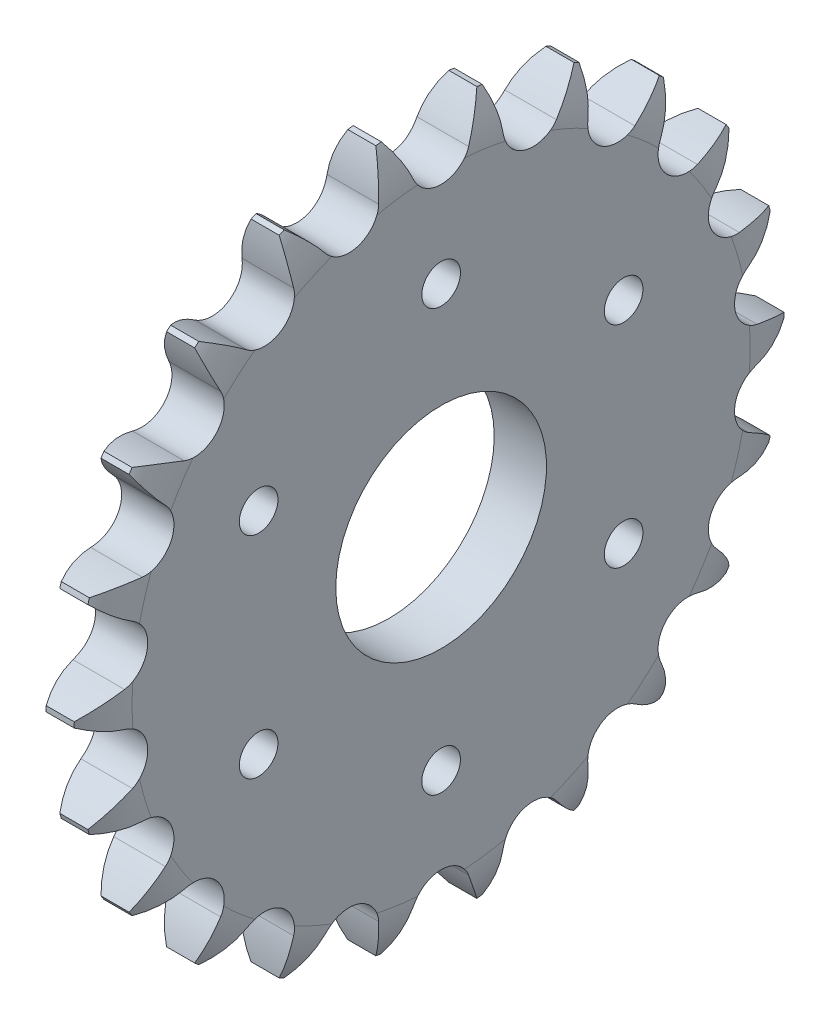
SolidWorks part; units mm, degrees
ref_plane "Plane1" through (0, 0, 0) normal (0, 0, 1) x (1, 0, 0)
ref_plane "Plane2" through (0, 0, 0) normal (0, 1, 0) x (1, 0, 0)
ref_plane "Plane3" through (0, 0, 0) normal (1, 0, 0) x (0, 0, -1)
sketch "Clipboard" plane through (0, 0, 0) normal (0, 1, 0) x (1, 0, 0)
  line L0 (0, 0) -> (14.719, -5.9469)
  line L1 (-15, 0) -> (100, 0) construction
  line L2 (0, 0) -> (-1.3675, 1.5456)
  line L3 (0, 0) -> (-14.8288, 5.6677)
  line L4 (0, 0) -> (2.8743, 1.1613)
  line L5 (0, 0) -> (-46.8476, -17.4728)
  line L6 (0, 0) -> (-7.4026, -4.9946)
  line L7 (-1.3675, 1.5456) -> (44.6582, 21.0824)
  line L8 (-76.2, 38.1) -> (-72.9, 38.1)
  line L9 (-73.5462, 42.5082) -> (-72.9534, 42.6013)
  line L10 (-74, 16.6356) -> (-55.89, 16.6356)
  circle A0 centre (0, 0) radius 5.08
  circle A1 centre (0, 0) radius 37.5
  circle A2 centre (0, 0) radius 37.5
  dimension "Num_teeth" = 22
  dimension "Thickness" = 8.93
sketch "BasProSke" plane through (0, 0, 0) normal (0, 1, 0) x (1, 0, 0)
  line L0 (-10, 0) -> (60, 0) construction
  line L1 (0, 0) -> (0, 52.7889)
  line L2 (0, 0) -> (8.93, 0)
  line L3 (8.93, 0) -> (8.93, 52.7889)
  line L4 (6.8663, 60.6161) -> (2.0638, 60.6161)
  arc A0 (0, 52.7889) -> (2.0638, 60.6161) centre (15.875, 52.7889) cw
  arc A1 (8.93, 52.7889) -> (6.8663, 60.6161) centre (-6.945, 52.7889) ccw
  dimension "D1" = 15.875
  dimension "Thickness" = 8.93
  dimension "Diameter" = 121.2322
revolve "Base-Revolve" add sketch "BasProSke" angle 360 about L0
sketch "TooCutSke" plane through (0, 0, 0) normal (1, 0, 0) x (0, 0, -1)
  line L0 (0, 55.825) -> (4.7557, 53.8992) construction
  line L1 (0, 0) -> (0, 107) construction
  line L2 (0, 55.825) -> (-10, 55.825) construction
  line L3 (0, 55.825) -> (-4.7557, 53.8992) construction
  arc A0 (4.7557, 53.8992) -> (8.5049, 60.5214) centre (31.8771, 42.9164) cw
  arc A1 (4.7557, 53.8992) -> (-4.7557, 53.8992) centre (0, 55.825) cw
  arc A2 (-4.7557, 53.8992) -> (-8.5049, 60.5214) centre (-31.8771, 42.9164) ccw
  arc A3 (8.5049, 60.5214) -> (-8.5049, 60.5214) centre (0, 0) ccw
extrude "ToothCut" cut sketch "TooCutSke" along normal through all
pattern_circular "TeethCuts" count 22 every 16.364 about axis through (-10, 0, 0) along (1, 0, 0) of "ToothCut"
sketch "HubNeaOneSke" plane through (0, 0, 0) normal (-1, 0, 0) x (0, 0, 1)
  circle A0 centre (0, 0) radius 37.5
  dimension "Diameter" = 75
extrude "HubNearOne" [suppressed] add sketch "HubNeaOneSke" along normal blind 41.0705
fillet "HubNearOneFillet" [suppressed] radius 0.6
sketch "HubNeaBotSke" plane through (0, 0, 0) normal (-1, 0, 0) x (0, 0, 1)
  circle A0 centre (0, 0) radius 37.5
  dimension "Diameter" = 75
extrude "HubNearBoth" [suppressed] add sketch "HubNeaBotSke" along normal blind 20.5353
fillet "HubNearBothFillet" [suppressed] radius 0.6
ref_plane "FarPln" through (8.93, 0, 0) normal (1, 0, 0) x (0, 0, -1)
sketch "HubFarSke" plane through (8.93, 0, 0) normal (1, 0, 0) x (0, 0, -1)
  circle A0 centre (0, 0) radius 37.5
  dimension "Diameter" = 75
extrude "HubFar" [suppressed] add sketch "HubFarSke" along normal blind 20.5353
fillet "HubFarFillet" [suppressed] radius 0.6
sketch "BorSke" plane through (0, 0, 0) normal (1, 0, 0) x (0, 0, -1)
  circle A0 centre (0, 0) radius 18
  dimension "Diameter" = 36
extrude "Bore" cut sketch "BorSke" along normal mid plane 100.001
sketch "KeySke" plane through (0, 0, 0) normal (1, 0, 0) x (0, 0, -1)
  line L0 (-5, 0) -> (-5, 21.3)
  line L1 (-5, 21.3) -> (5, 21.3)
  line L2 (5, 21.3) -> (5, 0)
  line L3 (0, 0) -> (0, 34) construction
  line L4 (-5, 0) -> (5, 0)
  dimension "Width" = 10
extrude "Keyway" [suppressed] cut sketch "KeySke" along normal mid plane 100.001
pattern_circular "Keyway2" [suppressed] count 2 every 90 about axis through (-10, 0, 0) along (1, 0, 0) reverse direction yes
ref_axis "Assi1" through (8.93, 0, 0) along (-1, 0, 0)
hole_wizard "Foro per Vite M6-1" positions "Schizzo2" profile "Schizzo3" hole size "M6" standard "ISO"
sketch "Schizzo2" plane through (8.93, 0, 0) normal (1, 0, 0) x (0, 0, -1)
  point P0 (0, 36)
  dimension "D1" = 36
sketch "Schizzo3" plane through (8.93, 36, 0) normal (0, 1, 0) x (0, 0, -1)
  line L0 (0, 0) -> (0, 12)
  line L1 (0, 12) -> (3.3, 10.0172)
  line L2 (3.3, 10.0172) -> (3.3, 0)
  line L5 (3.3, 0) -> (0, 0)
  line L10 (0, 12) -> (-3.3, 10.0172) construction
  line L11 (0, -6.35) -> (0, 107.95) construction
  dimension "Hole Dia." = 6.6
  dimension "Hole Depth" = 12
  dimension "Drill Angle" = 118
pattern_circular "RipetizioneCircolare1" count 6 over 360 about axis through (8.93, 0, 0) along (1, 0, 0) of "Foro per Vite M6-1"
equation "' \"Pitch@Clipboard\" = 12.7"
equation "' \"Num_strands@Clipboard\" = 1"
equation "' \"Num_teeth@Clipboard\" = 9"
equation "' \"Hub_dia@Clipboard\" = 50"
equation "' \"Overall_len@Clipboard\" = 3"
equation "' \"Diameter@BorSke\" = 12"
equation "' \"T_dim@Clipboard\" = 1"
equation "' \"Width@KeySke\" = 2"
equation "' \"Dr@Clipboard\" = 8.51"
equation "' \"Face_width@Clipboard\" = 7.2"
equation "' \"Side_radius@Clipboard\" = 12.7"
equation "' \"Side_relief@Clipboard\" = 1.27"
equation "' \"Transv_pitch@Clipboard\" = 13.92"
equation "' \"Show_teeth@Clipboard\" = 9"
equation "' \"Fillet_rad@Clipboard\" = 0.6"
equation "' \"Plate_wid@Clipboard\" = 11.8"
equation "\"Num_teeth@Clipboard\" = int( \"Num_teeth@Clipboard\" )"
equation "\"Num_teeth@Clipboard\" = ((sgn( \"Num_teeth@Clipboard\" - 5.0)+1)*( \"Num_teeth@Clipboard\" - 5.0))/2 +5.0"
equation "\"Num_teeth@Clipboard\" = ((sgn( \"Num_teeth@Clipboard\" - 200.0)-1)*( \"Num_teeth@Clipboard\" - 200.0))/-2 +200.0"
equation "\"MHD@Clipboard\" = \"Pitch@Clipboard\" * (1.0 / tan(3.14159265 / \"Num_teeth@Clipboard\" )) - 1.04 * \"Plate_wid@Clipboard\" - 0.76"
equation "\"Thickness@Clipboard\"  = \"Face_width@Clipboard\" + (\"Num_strands@Clipboard\" - 1) * \"Transv_pitch@Clipboard\""
equation "\"OAL@Clipboard\" = \"Thickness@Clipboard\" + 2 * \"Fillet_rad@Clipboard\" + 1"
equation "\"MHD@Clipboard\" = ((sgn( \"MHD@Clipboard\" - \"Hub_dia@Clipboard\" )-1)*( \"MHD@Clipboard\" - \"Hub_dia@Clipboard\" ))/-2+ \"Hub_dia@Clipboard\""
equation "\"OAL@Clipboard\" = ((sgn( \"OAL@Clipboard\" - \"Overall_len@Clipboard\" )+1)*( \"OAL@Clipboard\" - \"Overall_len@Clipboard\" ))/2 + \"Overall_len@Clipboard\" + 0.0005"
equation "\"Num_teeth@TeethCuts\" = int( \"Show_teeth@Clipboard\" ) + 1"
equation "\"Num_teeth@TeethCuts\" = ((sgn( \"Num_teeth@TeethCuts\" - \"Num_teeth@Clipboard\" )-1)*( \"Num_teeth@TeethCuts\" - \"Num_teeth@Clipboard\" ))/-2+ \"Num_teeth@Clipboard\""
equation "\"Num_teeth@TeethCuts\" = ((sgn( \"Num_teeth@TeethCuts\" - 2.0)+1)*( \"Num_teeth@TeethCuts\" - 2.0))/2 +2.0"
equation "\"Angle@TeethCuts\" = 360.0 / \"Num_teeth@Clipboard\""
equation "\"Seat_radius@TooCutSke\" = ( \"Pitch@Clipboard\" / 2.0) / sin(3.14159265 / \"Num_teeth@Clipboard\" ) - \"Dr@Clipboard\" / 2.0 + \"Dr@Clipboard\" * 0.505"
equation "\"R1@TooCutSke\"  = \"Dr@Clipboard\" * 0.505"
equation "\"X@TooCutSke\" = 140.0 - (90.0 / \"Num_teeth@Clipboard\")"
equation "\"R2@TooCutSke\" = 0.12 * \"Dr@Clipboard\" * ( \"Num_teeth@Clipboard\" + 2.0)"
equation "\"Overcut@TooCutSke\" = 0.5 + 0.625 * \"Pitch@Clipboard\" - 0.5 * \"Dr@Clipboard\"  +  \"Pitch@Clipboard\" / 2.0 / sin(3.14159265 / \"Num_teeth@Clipboard\" )"
equation "\"Diameter@BasProSke\" = 2.0 * ( 0.625 * \"Pitch@Clipboard\" - 0.5 * \"Dr@Clipboard\"  +  \"Pitch@Clipboard\" / 2.0 / sin(3.14159265 / \"Num_teeth@Clipboard\" ))"
equation "\"Thickness@BasProSke\"  = \"Thickness@Clipboard\""
equation "\"G1@BasProSke\" =  \"Side_relief@Clipboard\""
equation "\"G2@BasProSke\" =  \"Side_relief@Clipboard\""
equation "\"D1@BasProSke\" =  \"Side_radius@Clipboard\""
equation "\"Diameter@HubNeaOneSke\" = \"MHD@Clipboard\""
equation "\"Length@HubNearOne\" = \"OAL@Clipboard\" - \"Thickness@BasProSke\""
equation "\"Diameter@HubNeaBotSke\" = \"MHD@Clipboard\""
equation "\"Length@HubNearBoth\" = ( \"OAL@Clipboard\" - \"Thickness@BasProSke\" ) / 2.0"
equation "\"D1@HubNearOneFillet\" = \"Fillet_rad@Clipboard\""
equation "\"D1@HubNearBothFillet\" = \"Fillet_rad@Clipboard\""
equation "\"Thickness@FarPln\" = \"Thickness@BasProSke\""
equation "\"Diameter@HubFarSke\" = \"MHD@Clipboard\""
equation "\"Length@HubFar\" = ( \"OAL@Clipboard\" - \"Thickness@BasProSke\" ) / 2.0"
equation "\"D1@HubFarFillet\" = \"Fillet_rad@Clipboard\""
equation "\"D1@Bore\" = \"OAL@Clipboard\" * 2.0"
equation "\"D1@Keyway\" = \"OAL@Clipboard\" * 2.0"
equation "\"Offset@KeySke\" = \"T_dim@Clipboard\" + \"Diameter@BorSke\" / 2.0"
